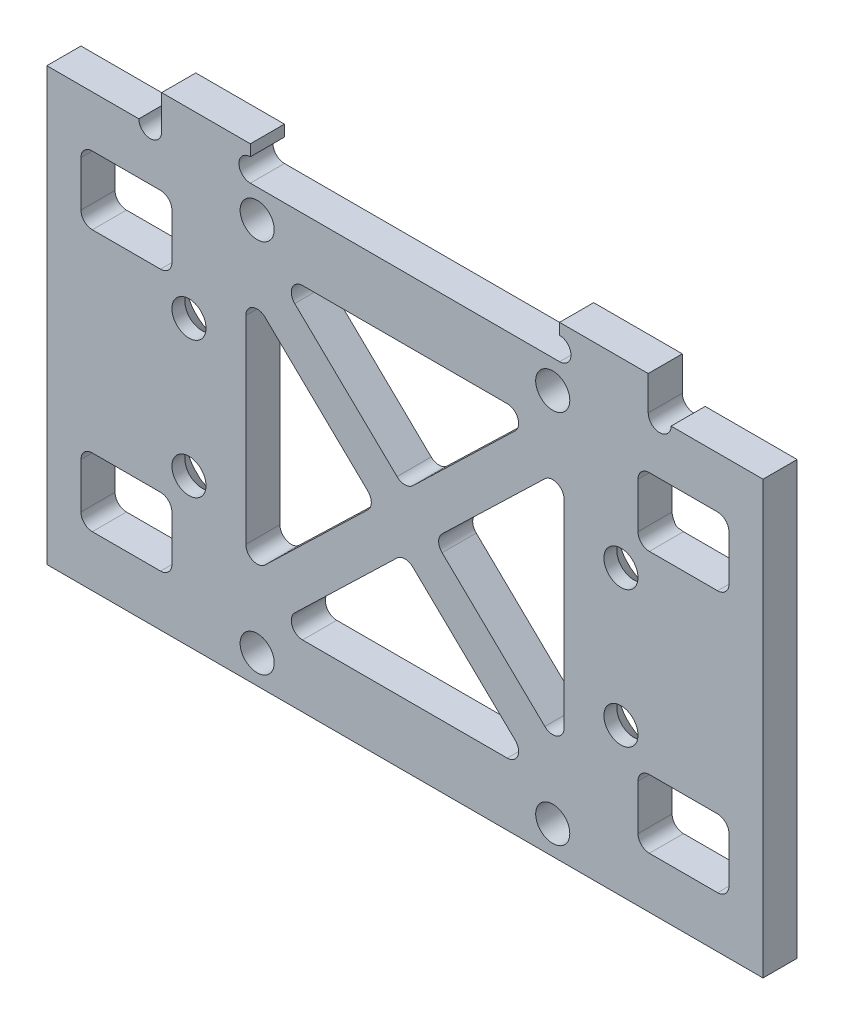
SolidWorks part; units mm, degrees
material "Thornel Mat VMA"
ref_plane "前视基准面" through (0, 0, 0) normal (0, 0, 1) x (1, 0, 0)
ref_plane "上视基准面" through (0, 0, 0) normal (0, 1, 0) x (1, 0, 0)
ref_plane "右视基准面" through (0, 0, 0) normal (1, 0, 0) x (0, 0, -1)
sketch "草图1" plane through (0, 0, 0) normal (0, 0, 1) x (1, 0, 0)
  line L0 (0, 0) -> (-12.4597, 0) construction
  line L1 (13, -16.5) -> (-13, -16.5) construction
  line L2 (13, -16.5) -> (13, 16.5) construction
  line L3 (13, 16.5) -> (-13, 16.5) construction
  line L4 (-13, -16.5) -> (-13, 16.5) construction
  line L5 (13, -16.5) -> (-13, 16.5) construction
  line L6 (13, 16.5) -> (-13, -16.5) construction
  line L7 (0, 0) -> (0, 10.3016) construction
  line L8 (-20.5, -14.5) -> (-28.5, -14.5)
  line L9 (31.5, -19) -> (-31.5, -19)
  line L10 (42, -19) -> (42, 19) construction
  line L11 (31.5, 19) -> (23.41, 19)
  line L12 (-42, -19) -> (-42, 19) construction
  line L13 (42, -19) -> (-42, 19) construction
  line L14 (42, 19) -> (-42, -19) construction
  line L15 (-20.5, 8.5) -> (-28.5, 8.5)
  line L16 (-20.5, 8.5) -> (-20.5, 14.5)
  line L17 (-20.5, 14.5) -> (-28.5, 14.5)
  line L18 (-28.5, 8.5) -> (-28.5, 14.5)
  line L19 (-20.5, 8.5) -> (-28.5, 14.5) construction
  line L20 (-20.5, 14.5) -> (-28.5, 8.5) construction
  line L21 (-28.5, -8.5) -> (-28.5, -14.5)
  line L22 (-20.5, -8.5) -> (-28.5, -8.5)
  line L23 (-20.5, -8.5) -> (-20.5, -14.5)
  line L24 (20.5, -8.5) -> (20.5, -14.5)
  line L25 (20.5, -8.5) -> (28.5, -8.5)
  line L26 (28.5, -8.5) -> (28.5, -14.5)
  line L27 (20.5, -14.5) -> (28.5, -14.5)
  line L28 (20.5, 14.5) -> (28.5, 14.5)
  line L29 (28.5, 8.5) -> (28.5, 14.5)
  line L30 (20.5, 8.5) -> (28.5, 8.5)
  line L31 (20.5, 8.5) -> (20.5, 14.5)
  line L32 (-28.5, -11.5) -> (-24.5, -11.5) construction
  line L33 (24.5, 14.5) -> (24.5, 12.5) construction
  line L35 (-31.5, 19) -> (-31.5, -19)
  line L36 (-21.4, 19) -> (-21.4, 22)
  line L37 (-21.4, 22) -> (-13.6, 22)
  line L38 (-13.6, 22) -> (-13.6, 21.01)
  line L39 (13.6, 22) -> (13.6, 21.01)
  line L40 (21.4, 22) -> (13.6, 22)
  line L41 (21.4, 19) -> (21.4, 22)
  line L42 (-17.5, 22) -> (-17.5, 20.2342) construction
  line L43 (17.5, 22) -> (17.5, 19.8079) construction
  line L44 (-23.41, 19) -> (-31.5, 19)
  line L45 (11.59, 19) -> (-11.59, 19)
  line L46 (-13.6, 19) -> (-11.59, 19)
  line L47 (11.59, 19) -> (13.6, 19)
  line L48 (-14, -11.0689) -> (-2.5211, 0)
  line L49 (14, -13.5) -> (-14, -13.5) construction
  line L50 (14, -13.5) -> (14, 13.5) construction
  line L51 (14, 13.5) -> (-14, 13.5) construction
  line L52 (-14, -13.5) -> (-14, 13.5) construction
  line L53 (14, -13.5) -> (-14, 13.5) construction
  line L54 (14, 13.5) -> (-14, -13.5) construction
  line L55 (-11.4789, -13.5) -> (0, -2.4311)
  line L56 (-11.4789, 13.5) -> (0, 2.4311)
  line L57 (-14, 11.0689) -> (-2.5211, 0)
  line L58 (0, 2.4311) -> (11.4789, 13.5)
  line L59 (-11.4789, 13.5) -> (11.4789, 13.5)
  line L60 (0, -2.4311) -> (11.4789, -13.5)
  line L61 (2.5211, 0) -> (14, 11.0689)
  line L62 (2.5211, 0) -> (14, -11.0689)
  line L63 (14, 11.0689) -> (14, -11.0689)
  line L64 (-11.4789, -13.5) -> (11.4789, -13.5)
  line L65 (-14, -11.0689) -> (-14, 11.0689)
  line L71 (38, 13) -> (38, -13) construction
  line L80 (31.5, 19) -> (31.5, -19)
  circle A0 centre (-13, 16.5) radius 1.5
  circle A1 centre (-13, -16.5) radius 1.5
  circle A2 centre (13, -16.5) radius 1.5
  circle A3 centre (13, 16.5) radius 1.5
  circle A4 centre (-38, 13) radius 1.5 construction
  circle A5 centre (-38, -13) radius 1.5 construction
  circle A8 centre (-19, 6) radius 1.5
  circle A9 centre (-19, -6) radius 1.5
  circle A10 centre (19, -6) radius 1.5
  circle A11 centre (19, 6) radius 1.5
  arc A12 (-23.41, 19) -> (-21.4, 19) centre (-22.405, 19) ccw
  arc A13 (-13.6, 19) -> (-11.59, 19) centre (-12.595, 19) ccw construction
  arc A14 (23.41, 19) -> (21.4, 19) centre (22.405, 19) cw
  arc A15 (13.6, 19) -> (11.59, 19) centre (12.595, 19) cw construction
  arc A16 (-13.6, 21.01) -> (-13.6, 19) centre (-13.6, 20.005) ccw
  arc A17 (13.6, 19) -> (13.6, 21.01) centre (13.6, 20.005) ccw
  point P0 (0, 0)
  point P25 (-24.5, 11.5)
  dimension "D1" = 3
  dimension "D13" = 38
  dimension "D14" = 3
  dimension "D18" = 2.01
  dimension "D2" = 33
  dimension "D3" = 26
  dimension "D4" = 26
  dimension "D5" = 76
  dimension "D6" = 2.5
  dimension "D7" = 4
  dimension "D8" = 6
  dimension "D9" = 8
  dimension "D10" = 49
  dimension "D11" = 23
  dimension "D12" = 12
  dimension "D15" = 3
  dimension "D16" = 7.8
  dimension "D17" = 3
  dimension "D19" = 35
  dimension "D20" = 3
  dimension "D21" = 5
  dimension "D22" = 3.5
extrude "凸台-拉伸1" add sketch "草图1" along normal blind 3
hole_wizard "M3 六角凹锥坑螺钉的锥形沉头孔1" positions "3D草图1" profile "草图2" countersink size "M3" standard "ISO" end condition through all
sketch3d "3D草图1"
  line L0 (19, 6, 3) -> (19, 6, 0) construction
  line L1 (-19, 6, 3) -> (-19, 6, 0) construction
  line L2 (-19, -6, 3) -> (-19, -6, 0) construction
  line L3 (19, -6, 3) -> (19, -6, 0) construction
  point P0 (19, 6, 0)
  point P4 (-19, 6, 0)
  point P8 (-19, -6, 0)
  point P12 (19, -6, 0)
sketch "草图2" plane through (19, 6, 0) normal (1, 0, 0) x (0, 1, 0)
  line L0 (0, 0) -> (0, 3)
  line L1 (0, 3) -> (1.5, 3)
  line L2 (1.5, 3) -> (1.5, 1.86)
  line L3 (1.5, 1.86) -> (3.36, 0)
  line L5 (3.36, 0) -> (0, 0)
  line L6 (-1.5, 1.86) -> (-3.36, 0) construction
  line L11 (0, -6.35) -> (0, 107.95) construction
  dimension "通孔孔直径" = 3
  dimension "通孔孔深度" = 3
  dimension "近端锥形沉头孔直径" = 6.72
  dimension "近端锥形沉头孔角度" = 90
fillet "圆角1" radius 1 28 edges at (28.5, 8.5, 1.5) (20.5, 14.5, 1.5) (20.5, 8.5, 1.7223) (20.5, -14.5, 1.5) (28.5, -14.5, 1.5) (28.5, -8.5, 1.5) (20.5, -8.5, 1.7223) (-28.5, -8.5, 1.5) (-28.5, -14.5, 1.5) (-20.5, -14.5, 1.5) (-20.5, -8.5, 1.7223) (-20.5, 8.5, 1.7223) (-20.5, 14.5, 1.5) (-28.5, 14.5, 1.5) (-28.5, 8.5, 1.5) (28.5, 14.5, 1.5) (2.5211, 0, 1.5) (14, -11.0689, 1.5) (14, 11.0689, 1.5) (0, -2.4311, 1.5) (-11.4789, -13.5, 1.5) (11.4789, -13.5, 1.5) (0, 2.4311, 1.5) (11.4789, 13.5, 1.5) (-2.5211, 0, 1.5) (-14, 11.0689, 1.5) (-14, -11.0689, 1.5) (-11.4789, 13.5, 1.5)
